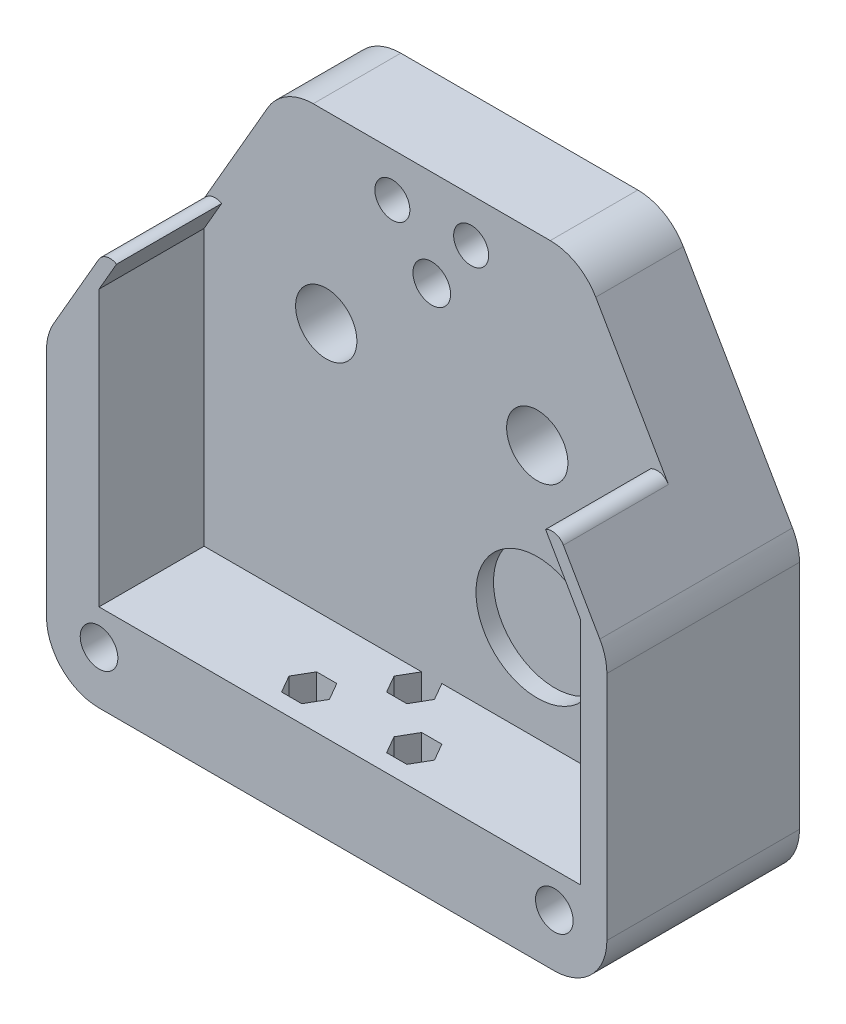
SolidWorks part; units mm, degrees
material "ABS"
ref_plane "Спереди" through (0, 0, 0) normal (0, 0, 1) x (1, 0, 0)
ref_plane "Сверху" through (0, 0, 0) normal (0, 1, 0) x (1, 0, 0)
ref_plane "Справа" through (0, 0, 0) normal (1, 0, 0) x (0, 0, -1)
sketch "Эскиз1" plane through (0, 0, 0) normal (0, 0, 1) x (1, 0, 0)
  line L0 (0, 0) -> (64, 0)
  line L1 (64, 0) -> (64, 34.0192)
  line L2 (64, 34.0192) -> (49, 60)
  line L3 (49, 60) -> (15, 60)
  line L4 (15, 60) -> (0, 34.02)
  line L5 (0, 34.02) -> (0, 0)
  dimension "D1" = 64
  dimension "D2" = 60
  dimension "D3" = 120
  dimension "D4" = 34
  dimension "D5" = 30
  dimension "D6" = 34.02
extrude "Бобышка-Вытянуть1" add sketch "Эскиз1" along normal blind 10
sketch "Эскиз3" plane through (0, 0, 10) normal (0, 0, 1) x (1, 0, 0)
  line L0 (0, 0) -> (64, 0)
  line L1 (64, 0) -> (64, 34.0192)
  line L2 (64, 34.0192) -> (58.2904, 43.9086)
  line L3 (64, 34.0192) -> (49, 60) construction
  line L4 (58.2904, 43.9086) -> (57, 43.1636)
  line L5 (57, 43.1636) -> (61, 36.2354)
  line L6 (61, 36.2354) -> (61, 10)
  line L7 (61, 10) -> (6, 10)
  line L8 (6, 10) -> (6, 41.4321)
  line L9 (6, 41.4321) -> (8, 44.8961)
  line L10 (8, 44.8961) -> (6.7097, 45.6412)
  line L11 (15, 60) -> (0, 34.02) construction
  line L12 (6.7097, 45.6412) -> (0, 34.02)
  line L13 (0, 34.02) -> (0, 0)
  dimension "D1" = 55
  dimension "D2" = 6
  dimension "D3" = 10
  dimension "D4" = 4
  dimension "D5" = 8
  dimension "D6" = 1.49
  dimension "D7" = 1.49
extrude "Бобышка-Вытянуть2" add sketch "Эскиз3" along normal blind 12
fillet "Скругление1" radius 6 6 edges at (64, 34.0192, 11) (49, 60, 5) (15, 60, 5) (0, 34.02, 11) (0, 0, 11) (64, 0, 11)
fillet "Скругление2" radius 1.49 2 edges at (58.2904, 43.9086, 16) (6.7097, 45.6412, 16)
hole_wizard "Зенковка для  винта с плоской головкой M44" positions "Эскиз13" profile "Эскиз14" countersink size "M4" standard "Ansi Metric" end condition through all
sketch "Эскиз13" plane through (0, 0, 0) normal (0, 0, -1) x (-1, 0, 0)
  line L3 (-32, 62.7004) -> (-32, -1.1162) construction
  line L5 (-45.5359, 60) -> (-18.4641, 60) construction
  line L6 (-6, 0) -> (-58, 0) construction
  line L7 (-64, 6) -> (-64, 32.4115) construction
  point P0 (-5.9999, 6)
  point P2 (-58, 6)
  point P4 (-32, 49)
  point P34 (-32, 60)
  dimension "D1" = 11
  dimension "D2" = 6
  dimension "D3" = 6
sketch "Эскиз14" plane through (5.9999, 6, 0) normal (1, 0, 0) x (0, 1, 0)
  line L0 (0, 0) -> (0, 22)
  line L1 (0, 22) -> (2.15, 22)
  line L2 (2.15, 22) -> (2.15, 2.2)
  line L3 (2.15, 2.2) -> (4.35, 0)
  line L5 (4.35, 0) -> (0, 0)
  line L6 (-2.15, 2.2) -> (-4.35, 0) construction
  line L11 (0, -3.8306) -> (0, 22.0892) construction
  dimension "Диаметр сквозного отверстия" = 4.3
  dimension "Глубина сквозного отверстия" = 22
  dimension "Диаметр передней зенковки" = 8.7
  dimension "Угол передней зенковки" = 90
hole_wizard "Отверстия под штифты Ø4.0 мм2" positions "Эскиз19" profile "Эскиз20" hole size "Ø4.0" standard "Ansi Metric"
sketch "Эскиз19" plane through (0, 0, 10) normal (0, 0, -1) x (-1, 0, 0)
  line L0 (-45.5359, 60) -> (-18.4641, 60) construction
  line L1 (-64, 6) -> (-64, 32.4115) construction
  line L8 (-32, 62.4273) -> (-32, -3.8376) construction
  point P0 (-36.5, 55)
  point P2 (-27.4999, 55)
  point P94 (-32, 60)
  dimension "D1" = 5
  dimension "D2" = 27.5
sketch "Эскиз20" plane through (36.5, 55, 10) normal (1, 0, 0) x (0, -1, 0)
  line L0 (0, 0) -> (0, 7.2017)
  line L1 (0, 7.2017) -> (2, 6)
  line L2 (2, 6) -> (2, 0)
  line L5 (2, 0) -> (0, 0)
  line L10 (0, 7.2017) -> (-2, 6) construction
  line L11 (0, -6.35) -> (0, 107.95) construction
  dimension "Диаметр отверстия" = 4
  dimension "Глубина отверстия" = 6
  dimension "Угол заточки сверла" = 118
hole_wizard "Диаметр отверстия Ø7.0 (7)1" positions "Эскиз21" profile "Эскиз22" hole size "Ø7.0" standard "DIN"
sketch "Эскиз21" plane through (0, 0, 10) normal (0, 0, -1) x (-1, 0, 0)
  line L0 (-45.5359, 60) -> (-18.4641, 60) construction
  line L1 (-64, 6) -> (-64, 32.4115) construction
  line L2 (-32, 62.1722) -> (-32, -3.1086) construction
  point P0 (-44.05, 39)
  point P2 (-19.9499, 39)
  point P18 (-32, 60)
  dimension "D1" = 21
  dimension "D2" = 19.95
sketch "Эскиз22" plane through (44.05, 39, 10) normal (1, 0, 0) x (0, -1, 0)
  line L0 (0, 0) -> (0, 8.103)
  line L1 (0, 8.103) -> (3.5, 6)
  line L2 (3.5, 6) -> (3.5, 0)
  line L5 (3.5, 0) -> (0, 0)
  line L10 (0, 8.103) -> (-3.5, 6) construction
  line L11 (0, -6.35) -> (0, 107.95) construction
  dimension "Диаметр отверстия" = 7
  dimension "Глубина отверстия" = 6
  dimension "Угол заточки сверла" = 118
ref_plane "Плоскость2" through (0, 10, 0) normal (0, -1, 0) x (-1, 0, 0)
hole_wizard "Отверстия под штифты Ø4.0 мм3" [suppressed] positions "Эскиз52" profile "Эскиз53" hole size "Ø4.0" standard "Ansi Metric"
sketch "Эскиз52" plane through (0, 0, 10) normal (0, 0, 1) x (1, 0, 0)
  line L0 (64, 6) -> (64, 32.4115) construction
  line L1 (6, 0) -> (58, 0) construction
  point P0 (44.05, 21)
  dimension "D1" = 19.95
  dimension "D2" = 21
sketch "Эскиз53" plane through (44.05, 21, 10) normal (1, 0, 0) x (0, -1, 0)
  line L0 (0, 0) -> (0, 13.2017)
  line L1 (0, 13.2017) -> (2, 12)
  line L2 (2, 12) -> (2, 0)
  line L5 (2, 0) -> (0, 0)
  line L10 (0, 13.2017) -> (-2, 12) construction
  line L11 (0, -6.35) -> (0, 107.95) construction
  dimension "Диаметр отверстия" = 4
  dimension "Глубина отверстия" = 12
  dimension "Угол заточки сверла" = 118
sketch "Эскиз54" plane through (0, 0, 10) normal (0, 0, 1) x (1, 0, 0)
  line L0 (64, 6) -> (64, 32.4115) construction
  line L1 (6, 0) -> (58, 0) construction
  circle A0 centre (44.05, 21) radius 7
  dimension "D1" = 14
  dimension "D2" = 19.95
  dimension "D3" = 21
extrude "Вырез-Вытянуть5" cut sketch "Эскиз54" against normal blind 2
sketch "Эскиз55" plane through (0, 0, 10) normal (0, 0, 1) x (1, 0, 0)
  circle A0 centre (19.9499, 39) radius 5
  circle A1 centre (19.9499, 39) radius 3.5 construction
  circle A2 centre (44.05, 39) radius 5
  circle A3 centre (44.05, 39) radius 3.5 construction
  dimension "D1" = 10
  dimension "D2" = 10
extrude "Вырез-Вытянуть9" [suppressed] cut sketch "Эскиз55" against normal blind 1.5
hole_wizard "Сверло под метчик  спиральное M2.21" positions "Эскиз56" profile "Эскиз57" hole size "M2.2x0.45" standard "Ansi Metric"
sketch "Эскиз56" plane through (0, 0, 0) normal (0, -1, 0) x (-1, 0, 0)
  line L0 (-6, -22) -> (-58, -22) construction
  line L1 (-32, -19.1422) -> (-32, -5.5593) construction
  line L3 (-6, -22) -> (-6, 0) construction
  point P0 (-26, -18)
  point P2 (-38, -18)
  point P15 (-32, -22)
  dimension "D1" = 4
  dimension "D2" = 20
sketch "Эскиз57" plane through (26, 0, 18) normal (1, 0, 0) x (0, 0, -1)
  line L0 (0, 0) -> (0, 10.6009)
  line L1 (0, 10.6009) -> (1, 10)
  line L2 (1, 10) -> (1, 0)
  line L5 (1, 0) -> (0, 0)
  line L10 (0, 10.6009) -> (-1, 10) construction
  line L11 (0, -6.35) -> (0, 14.5802) construction
  dimension "Диаметр отверстия" = 2
  dimension "Глубина отверстия" = 10
  dimension "Угол заточки сверла" = 118
sketch "Эскиз58" plane through (0, 10, 0) normal (0, 1, 0) x (1, 0, 0)
  line L0 (26, -10.8602) -> (26, -17.0191) construction
  line L1 (28.3094, -18) -> (27.1547, -16)
  line L2 (27.1547, -16) -> (24.8453, -16)
  line L3 (24.8453, -16) -> (23.6906, -18)
  line L4 (23.6906, -18) -> (24.8453, -20)
  line L5 (24.8453, -20) -> (27.1547, -20)
  line L6 (27.1547, -20) -> (28.3094, -18)
  line L9 (38, -10.8602) -> (38, -17.0191) construction
  line L10 (40.3094, -18) -> (39.1547, -16)
  line L11 (39.1547, -16) -> (36.8453, -16)
  line L12 (36.8453, -16) -> (35.6906, -18)
  line L13 (35.6906, -18) -> (36.8453, -20)
  line L14 (36.8453, -20) -> (39.1547, -20)
  line L15 (39.1547, -20) -> (40.3094, -18)
  circle A0 centre (26, -18) radius 2 construction
  circle A1 centre (38, -18) radius 2 construction
  dimension "D1" = 4
  dimension "D2" = 30
  dimension "D3" = 4
  dimension "D4" = 30
extrude "Вырез-Вытянуть11" cut sketch "Эскиз58" against normal blind 4
hole_wizard "Сверло под метчик  спиральное M2.22" positions "Эскиз59" profile "Эскиз60" hole size "M2.2x0.45" standard "Ansi Metric"
sketch "Эскиз59" plane through (0, 0, 0) normal (0, -1, 0) x (-1, 0, 0)
  line L0 (-6, -22) -> (-58, -22) construction
  line L1 (-58, 0) -> (-58, -22) construction
  point P0 (-32, -12)
  dimension "D1" = 10
  dimension "D2" = 26
sketch "Эскиз60" plane through (32, 0, 12) normal (1, 0, 0) x (0, 0, -1)
  line L0 (0, 0) -> (0, 10.6009)
  line L1 (0, 10.6009) -> (1, 10)
  line L2 (1, 10) -> (1, 0)
  line L5 (1, 0) -> (0, 0)
  line L10 (0, 10.6009) -> (-1, 10) construction
  line L11 (0, -6.35) -> (0, 21.1048) construction
  dimension "Диаметр отверстия" = 2
  dimension "Глубина отверстия" = 10
  dimension "Угол заточки сверла" = 118
sketch "Эскиз61" plane through (0, 10, 0) normal (0, 1, 0) x (1, 0, 0)
  line L0 (32, -5.2203) -> (32, -10.1362) construction
  line L1 (34.3094, -12) -> (33.1547, -10)
  line L2 (33.1547, -10) -> (30.8453, -10)
  line L3 (30.8453, -10) -> (29.6906, -12)
  line L4 (29.6906, -12) -> (30.8453, -14)
  line L5 (30.8453, -14) -> (33.1547, -14)
  line L6 (33.1547, -14) -> (34.3094, -12)
  circle A0 centre (32, -12) radius 2 construction
  dimension "D1" = 4
  dimension "D2" = 30
extrude "Вырез-Вытянуть12" cut sketch "Эскиз61" against normal blind 4
sketch "Эскиз62" plane through (0, 10, 0) normal (0, 1, 0) x (1, 0, 0)
  line L0 (32, -1012) -> (32, 48988) construction
  line L1 (34.3094, -12) -> (33.1547, -10)
  line L2 (33.1547, -10) -> (30.8453, -10)
  line L3 (30.8453, -10) -> (29.6906, -12)
  line L4 (29.6906, -12) -> (30.8453, -14)
  line L5 (30.8453, -14) -> (33.1547, -14)
  line L6 (33.1547, -14) -> (34.3094, -12)
  line L10 (45.5359, -10) -> (18.4641, -10) construction
  circle A0 centre (32, -12) radius 2 construction
  circle A1 centre (32, -12) radius 1 construction
  point P1 (0, 0)
  dimension "D1" = 4
  dimension "D2" = 30
